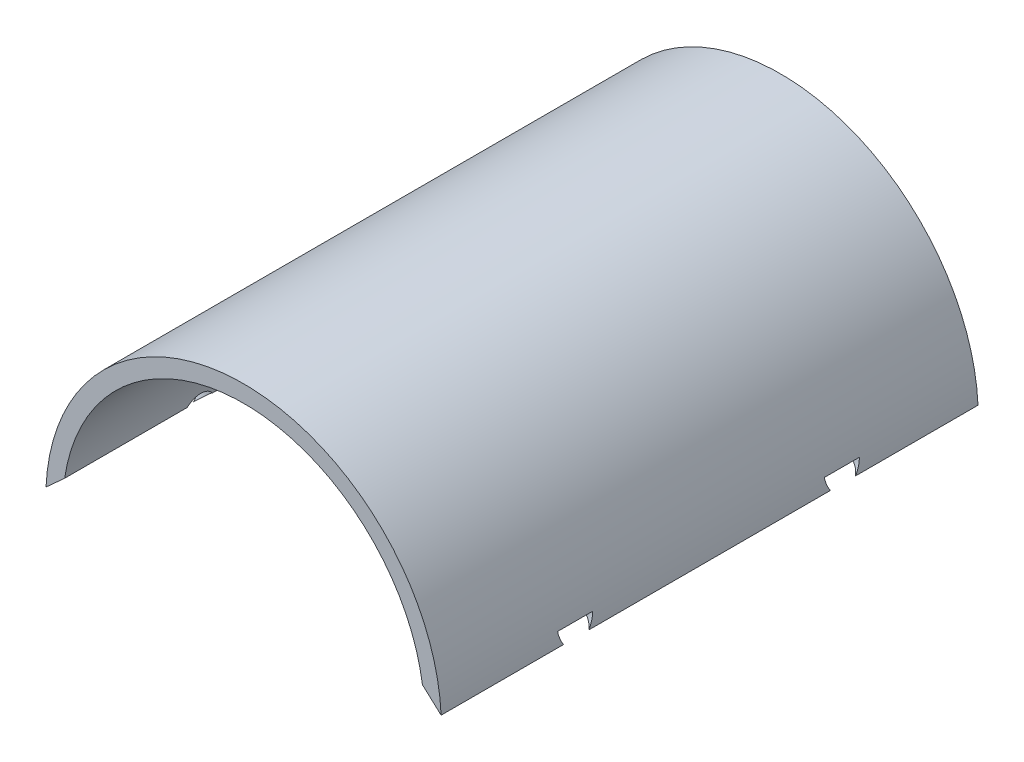
SolidWorks part; units mm, degrees
ref_plane "Front Plane" through (0, 0, 0) normal (0, 0, 1) x (1, 0, 0)
ref_plane "Top Plane" through (0, 0, 0) normal (0, 1, 0) x (1, 0, 0)
ref_plane "Right Plane" through (0, 0, 0) normal (1, 0, 0) x (0, 0, -1)
sketch "Sketch1" plane through (0, 0, 0) normal (0, 0, 1) x (1, 0, 0)
  line L0 (0, 0) -> (0, 44.45) construction
  line L1 (-40.2039, 5.9378) -> (40.2039, 5.9378) construction
  line L2 (-44.399, 2.1278) -> (44.399, 2.1278) construction
  line L3 (-40.2039, 5.9378) -> (-44.399, 2.1278)
  line L4 (40.2039, 5.9378) -> (44.399, 2.1278)
  arc A0 (44.399, 2.1278) -> (-44.399, 2.1278) centre (0, 0) ccw
  arc A1 (40.2039, 5.9378) -> (-40.2039, 5.9378) centre (0, 0) ccw
  dimension "D1" = 88.9
  dimension "D2" = 3.81
  dimension "D3" = 3.81
extrude "Boss-Extrude1" add sketch "Sketch1" along normal blind 120.65
sketch "Sketch2" plane through (-21.1272, 23.263, 0) normal (0.6723, -0.7403, 0) x (0.7403, 0.6723, 0)
  line L0 (-28.6033, 120.65) -> (-28.6033, 0) construction
  line L1 (-31.4368, 120.65) -> (-25.7698, 120.65) construction
  line L2 (-31.4368, 0) -> (-25.7698, 0) construction
  line L3 (-31.4368, 60.325) -> (-25.7698, 60.325) construction
  line L4 (-31.4368, 120.65) -> (-31.4368, 0) construction
  line L5 (-25.7698, 120.65) -> (-25.7698, 0) construction
  circle A0 centre (-28.6033, 90.297) radius 4
  circle A1 centre (-28.6033, 30.353) radius 4
  dimension "D1" = 8
  dimension "D2" = 29.972
extrude "Cut-Extrude1" cut sketch "Sketch2" against normal blind 2
sketch "Sketch3" plane through (21.1272, 23.263, 0) normal (-0.6723, -0.7403, 0) x (-0.7403, 0.6723, 0)
  line L0 (-28.6033, -120.65) -> (-28.6033, 0) construction
  line L1 (-25.7698, -120.65) -> (-31.4368, -120.65) construction
  line L2 (-25.7698, 0) -> (-31.4368, 0) construction
  line L3 (-25.7698, -60.325) -> (-31.4368, -60.325) construction
  line L4 (-25.7698, -120.65) -> (-25.7698, 0) construction
  line L5 (-31.4368, -120.65) -> (-31.4368, 0) construction
  circle A0 centre (-28.6033, -90.297) radius 4
  circle A1 centre (-28.6033, -30.353) radius 4
  dimension "D1" = 8
  dimension "D2" = 29.972
extrude "Cut-Extrude2" cut sketch "Sketch3" against normal blind 2.032
